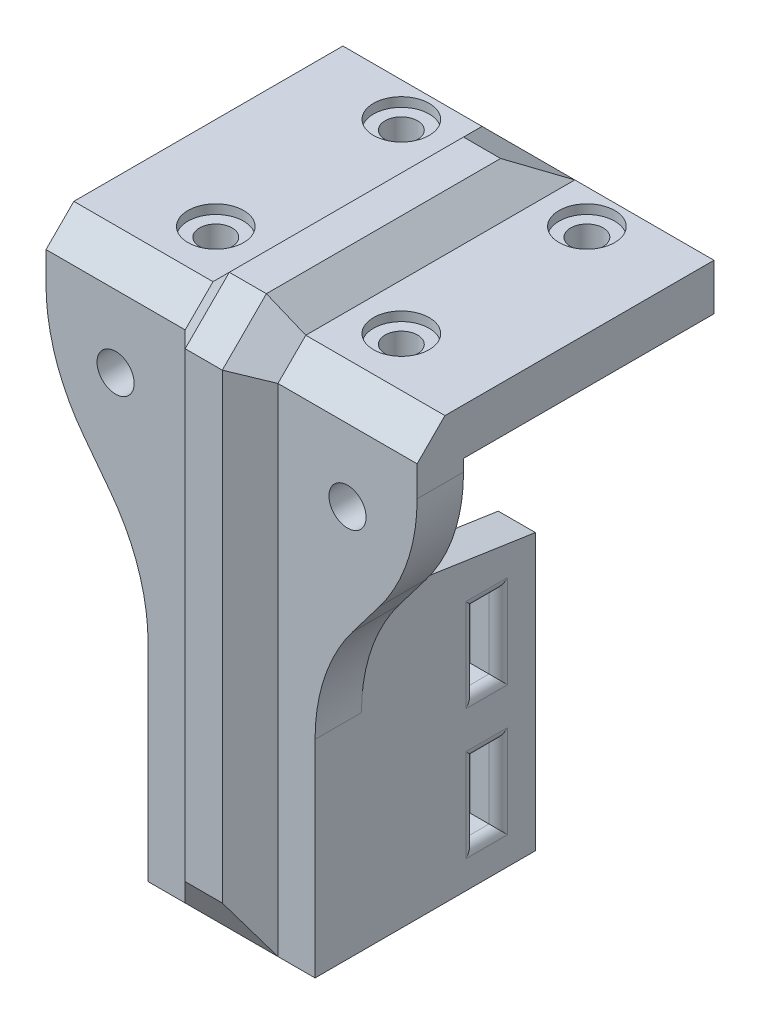
SolidWorks part; units mm, degrees
material "ABS"
ref_plane "Front Plane" through (0, 0, 0) normal (0, 0, 1) x (1, 0, 0)
ref_plane "Top Plane" through (0, 0, 0) normal (0, 1, 0) x (1, 0, 0)
ref_plane "Right Plane" through (0, 0, 0) normal (1, 0, 0) x (0, 0, -1)
sketch "Sketch1" plane through (0, 0, 0) normal (1, 0, 0) x (0, 0, -1)
  line L0 (0, 0) -> (0, -56.5)
  line L1 (0, 0) -> (32, 0)
  line L2 (32, 0) -> (32, -5)
  line L3 (32, -5) -> (5, -5)
  line L4 (5, -5) -> (5, -56.5)
  line L5 (5, -56.5) -> (0, -56.5)
  dimension "D1" = 5
  dimension "D2" = 27
  dimension "D3" = 51.5
extrude "Boss-Extrude1" add sketch "Sketch1" along normal blind 40
sketch "Sketch2" plane through (0, 0, -5) normal (0, 0, -1) x (-1, 0, 0)
  line L0 (-62.1629, -48.5) -> (-19.2032, -48.5) construction
  line L1 (-40, -5) -> (0, -5) construction
  line L2 (-19.2032, -34.5) -> (-60.1565, -34.5) construction
  line L3 (-46.7611, -24) -> (9.417, -24) construction
  line L4 (-40, -56.5) -> (-40, -5) construction
  line L5 (-40, -27.5) -> (0, -27.5)
  line L6 (-40, -27.5) -> (-40, -56.5)
  line L7 (-40, -56.5) -> (0, -56.5)
  line L8 (0, -27.5) -> (0, -56.5)
  dimension "D1" = 14
  dimension "D2" = 43.5
  dimension "D3" = 19
  dimension "D4" = 7
extrude "Boss-Extrude2" add sketch "Sketch2" along normal blind 23.5
sketch "Sketch3" plane through (40, 0, 0) normal (1, 0, 0) x (0, 0, -1)
  line L0 (5, -27.5) -> (5, -5) construction
  line L1 (17.25, -30.5) -> (19.75, -30.5)
  line L2 (17.25, -30.5) -> (17.25, -38.5)
  line L3 (17.25, -38.5) -> (19.75, -38.5)
  line L4 (19.75, -30.5) -> (19.75, -38.5)
  line L5 (17.25, -30.5) -> (19.75, -38.5) construction
  line L6 (17.25, -38.5) -> (19.75, -30.5) construction
  line L7 (17.25, -44.5) -> (19.75, -44.5)
  line L8 (17.25, -44.5) -> (17.25, -52.5)
  line L9 (17.25, -52.5) -> (19.75, -52.5)
  line L10 (19.75, -44.5) -> (19.75, -52.5)
  line L11 (17.25, -44.5) -> (19.75, -52.5) construction
  line L12 (17.25, -52.5) -> (19.75, -44.5) construction
  line L13 (5, -5) -> (32, -5) construction
  point P0 (18.5, -34.5)
  point P5 (18.5, -48.5)
  dimension "D1" = 13.5
  dimension "D2" = 14
  dimension "D3" = 43.5
  dimension "D4" = 2.5
  dimension "D5" = 8
extrude "Cut-Extrude1" cut sketch "Sketch3" against normal through all
sketch "Sketch4" plane through (0, 0, -28.5) normal (0, 0, -1) x (-1, 0, 0)
  line L0 (-40, -27.5) -> (0, -27.5) construction
  line L1 (-25, -27.5) -> (-15, -27.5)
  line L2 (-25, -27.5) -> (-25, -56.5)
  line L3 (-25, -56.5) -> (-15, -56.5)
  line L4 (-15, -27.5) -> (-15, -56.5)
  line L5 (-40, -56.5) -> (0, -56.5) construction
  line L6 (-40, 0) -> (0, 0) construction
  point P8 (-20, -27.5)
  point P11 (-20, 0)
  dimension "D1" = 10
extrude "Cut-Extrude2" cut sketch "Sketch4" against normal up to surface (11.25 mm away) up to face at (20, -34.5, -17.25)
sketch "Sketch5" plane through (0, 0, -28.5) normal (0, 0, -1) x (-1, 0, 0)
  line L0 (-29, -27.5) -> (-29, -56.5)
  line L1 (-40, -27.5) -> (0, -27.5) construction
  line L2 (-40, -56.5) -> (0, -56.5) construction
  line L3 (-29, -56.5) -> (-40, -56.5)
  line L4 (-40, -56.5) -> (-40, -13)
  line L5 (-40, -27.5) -> (-40, -5) construction
  line L6 (-40, -13) -> (-29, -27.5)
  line L7 (-40, -5) -> (0, -5) construction
  line L8 (-25, -27.5) -> (-25, -56.5) construction
  line L9 (-20, -12.0262) -> (-20, -39.653) construction
  line L10 (-40, -5) -> (0, -5) construction
  line L11 (0, -56.5) -> (0, -13)
  line L12 (-11, -56.5) -> (0, -56.5)
  line L13 (-11, -27.5) -> (-11, -56.5)
  line L14 (0, -13) -> (-11, -27.5)
  point P20 (-20, -5)
  dimension "D1" = 8
  dimension "D2" = 4
extrude "Cut-Extrude3" cut sketch "Sketch5" against normal through all
fillet "Fillet1" radius 20 4 edges at (0, -13, -2.5) (40, -13, -2.5) (11, -27.5, -2.5) (29, -27.5, -2.5)
sketch "Sketch6" plane through (0, 0, -17.25) normal (0, 0, -1) x (-1, 0, 0)
  line L0 (-40, -5) -> (0, -5) construction
  line L1 (-29, -56.5) -> (-29, -27.5) construction
  circle A0 centre (-20, -42) radius 2
  point P5 (-20, -5)
  point P8 (-29, -42)
  dimension "D1" = 4
extrude "Cut-Extrude4" cut sketch "Sketch6" against normal offset from surface (15.25 mm away) 2 up to face at (20, -22.9167, 0)
sketch "Sketch7" plane through (0, 0, 0) normal (0, 1, 0) x (1, 0, 0)
  line L0 (40, 5) -> (0, 5) construction
  line L1 (10, 28.3) -> (30, 28.3) construction
  line L2 (10, 28.3) -> (10, 8.3) construction
  line L3 (10, 8.3) -> (30, 8.3) construction
  line L4 (30, 28.3) -> (30, 8.3) construction
  line L5 (10, 28.3) -> (30, 8.3) construction
  line L6 (10, 8.3) -> (30, 28.3) construction
  line L7 (40, 0) -> (0, 0) construction
  circle A0 centre (30, 28.3) radius 1.75
  circle A1 centre (30, 8.3) radius 1.75
  circle A2 centre (10, 8.3) radius 1.75
  circle A3 centre (10, 28.3) radius 1.75
  point P0 (20, 18.3)
  point P10 (20, 0)
  dimension "D4" = 3.5
  dimension "D1" = 3.3
  dimension "D2" = 20
  dimension "D3" = 20
extrude "Cut-Extrude5" cut sketch "Sketch7" against normal up to next
sketch "Sketch8" plane through (0, 0, 0) normal (0, 1, 0) x (1, 0, 0)
  circle A0 centre (30, 28.3) radius 3
  circle A1 centre (30, 8.3) radius 3
  circle A2 centre (10, 8.3) radius 3
  circle A3 centre (10, 28.3) radius 3
  dimension "D1" = 6
extrude "Cut-Extrude6" cut sketch "Sketch8" against normal blind 1
ref_plane "Plane1" through (20, 0, 0) normal (-1, 0, 0) x (0, 0, 1)
sketch "Sketch9" plane through (20, 0, 0) normal (-1, 0, 0) x (0, 0, 1)
  line L0 (-32, 0) -> (0, 0)
  line L1 (0, 0) -> (0, -56.5)
  line L2 (0, -56.5) -> (3, -56.5)
  line L3 (3, -56.5) -> (3, 3)
  line L4 (3, 3) -> (-32, 3)
  line L5 (-32, 3) -> (-32, 0)
  dimension "D1" = 3
extrude "Boss-Extrude4" add sketch "Sketch9" along normal blind 2 and the other way blind 2
chamfer "Chamfer1" distance 3 distance2 5 1 edges at (20, 3, -32) first distance on face at (20, -0.5, -32)
chamfer "Chamfer2" distance 5 distance2 3 1 edges at (20, -56.5, 3) first distance on face at (20, -26.75, 3)
chamfer "Chamfer3" distance 3 distance2 3 3 edges at (20, 3, 3) (31, 0, 0) (9, 0, 0)
chamfer "Chamfer4" distance 3 angle 45 6 edges at (18, -29.75, 0) (18, -1.5, -1.5) (18, 0, -17.5) (22, -29.75, 0) (22, -1.5, -1.5) (22, 0, -17.5)
sketch "Sketch10" plane through (18, 0, 0) normal (-1, 0, 0) x (0, 0, 1)
  line L0 (-1.7574, 3) -> (3, -1.7574)
  line L1 (3, -1.7574) -> (3, 0)
  line L2 (3, 0) -> (0, 3)
  line L3 (0, 3) -> (-1.7574, 3)
extrude "Cut-Extrude7" cut sketch "Sketch10" against normal up to next
sketch "Sketch11" plane through (11, 0, 0) normal (-1, 0, 0) x (0, 0, 1)
  line L0 (-28.5, -27.5) -> (-5, -27.5) construction
  line L1 (-5, -6.2722) -> (-5, -18.36) construction
  line L2 (-32, -5) -> (-5, -5) construction
  line L3 (-32, -5) -> (-32, -13) construction
  line L4 (-32, -13) -> (-5, -13) construction
  line L5 (-5, -5) -> (-5, -13) construction
  line L6 (-5, -27.5) -> (-5, -16.5)
  line L7 (-24.5, -18) -> (-12.5, -18) construction
  line L8 (-24.5, -18) -> (-24.5, -8.5119) construction
  line L9 (-24.5, -8.5119) -> (-12.5, -8.5119) construction
  line L10 (-12.5, -18) -> (-12.5, -8.5119) construction
  line L11 (-24.5, -18) -> (-12.5, -8.5119) construction
  line L12 (-24.5, -8.5119) -> (-12.5, -18) construction
  line L13 (-25.5, -24) -> (-11.5, -24) construction
  line L14 (-25.5, -24) -> (-25.5, -15.5982) construction
  line L15 (-25.5, -15.5982) -> (-11.5, -15.5982) construction
  line L16 (-11.5, -24) -> (-11.5, -15.5982) construction
  line L17 (-25.5, -24) -> (-11.5, -15.5982) construction
  line L18 (-25.5, -15.5982) -> (-11.5, -24) construction
  line L19 (-5, -16.5) -> (-9.8595, -24.7238)
  line L20 (-28.5, -27.5) -> (-9.8595, -24.7238)
  line L21 (-28.5, -27.5) -> (-5, -27.5)
  point P11 (-18.5, -13.256)
  point P16 (-18.5, -19.7991)
  point P22 (-18.5, -5)
  line M4 (-5, -27.5) -> (-28.5, -27.5)
  dimension "D1" = 8
  dimension "D2" = 13
  dimension "D3" = 19
  dimension "D4" = 14
  dimension "D5" = 12
  dimension "D6" = 3.5
extrude "Boss-Extrude5" add sketch "Sketch11" against normal up to surface (18 mm away) contours L20 L6 L19 M4 region at (11, -24.9233, -10.9255) up to face at (29, -39.4093, -11.1667)
sketch "Sketch12" plane through (0, -27.5, 0) normal (0, -1, 0) x (1, 0, 0)
  line L1 (25, -28.5) -> (15, -28.5)
  line L2 (25, -28.5) -> (25, -17.25)
  line L3 (25, -17.25) -> (15, -17.25)
  line L4 (15, -28.5) -> (15, -17.25)
extrude "Cut-Extrude8" cut sketch "Sketch12" against normal blind 2
fillet "Fillet2" radius 1 28 edges at (25, -52.5, -18.5) (25, -48.5, -19.75) (25, -44.5, -18.5) (25, -38.5, -18.5) (25, -34.5, -19.75) (25, -30.5, -18.5) (29, -38.5, -18.5) (29, -34.5, -17.25) (29, -34.5, -19.75) (29, -30.5, -18.5) (29, -44.5, -18.5) (29, -48.5, -17.25) (29, -52.5, -18.5) (29, -48.5, -19.75) (15, -44.5, -18.5) (15, -48.5, -19.75) (15, -52.5, -18.5) (15, -38.5, -18.5) (15, -34.5, -19.75) (15, -30.5, -18.5) (11, -52.5, -18.5) (11, -48.5, -19.75) (11, -44.5, -18.5) (11, -48.5, -17.25) (11, -34.5, -17.25) (11, -30.5, -18.5) (11, -34.5, -19.75) (11, -38.5, -18.5)
sketch "Sketch13" plane through (29, 0, 0) normal (1, 0, 0) x (0, 0, -1)
  line L1 (28.5, -56.5) -> (23.75, -56.5)
  line L2 (28.5, -56.5) -> (28.5, -24.4192)
  line L3 (28.5, -24.4192) -> (23.75, -24.4192)
  line L4 (23.75, -56.5) -> (23.75, -24.4192)
  line L6 (19.75, -52.5) -> (19.75, -44.5) construction
  dimension "D1" = 4
extrude "Cut-Extrude9" cut sketch "Sketch13" against normal through all
sketch "Sketch14" plane through (0, 0, -5) normal (0, 0, -1) x (-1, 0, 0)
  line L0 (-20, -3.4497) -> (-20, 3.4497) construction
  line L1 (-40, -5) -> (0, -5) construction
  line L3 (-29, -16.5) -> (-29, -5) construction
  line L4 (-40, -5) -> (0, -5) construction
  circle A0 centre (-32.5, -10.75) radius 2
  circle A1 centre (-7.5, -10.75) radius 2
  dimension "D5" = 4
  dimension "D1" = 25
  dimension "D2" = 12.5
  dimension "D3" = 5.75
  dimension "D4" = 11.5
extrude "Cut-Extrude10" cut sketch "Sketch14" against normal up to next
equation "\"D2@Sketch14\"=\"D1@Sketch14\"/2"
equation "\"D3@Sketch14\"=\"D4@Sketch14\"/2"
